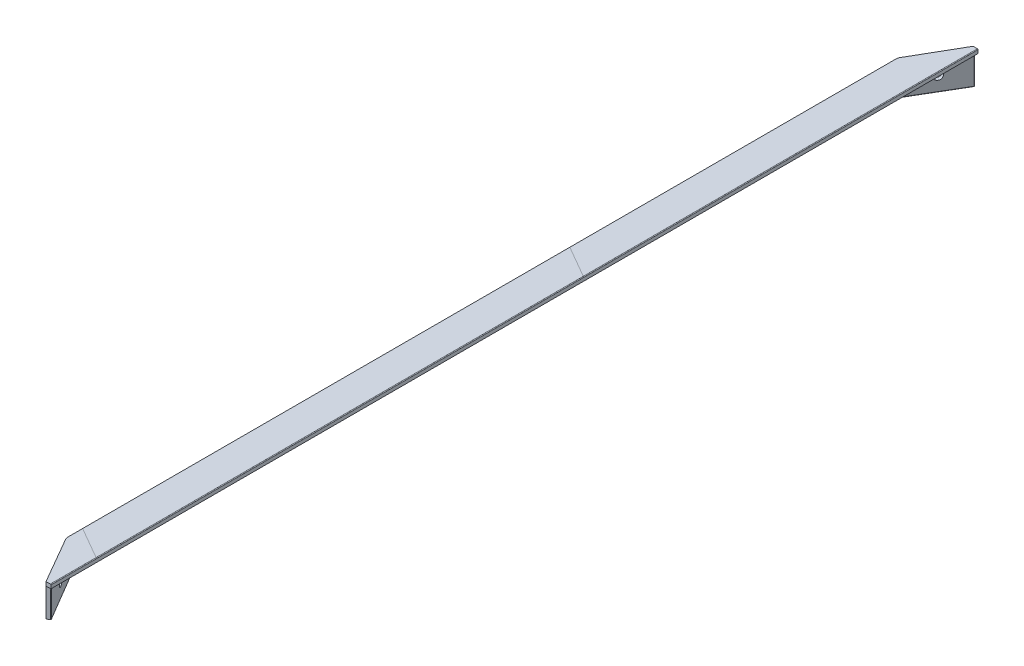
SolidWorks part; units mm, degrees
material "1.0116 (S235J2G3)"
ref_plane "Front Plane" through (0, 0, 0) normal (0, 0, 1) x (1, 0, 0)
ref_plane "Top Plane" through (0, 0, 0) normal (0, 1, 0) x (1, 0, 0)
ref_plane "Right Plane" through (0, 0, 0) normal (1, 0, 0) x (0, 0, -1)
sketch "Sketch1" plane through (0, 0, 0) normal (0, 0, 1) x (1, 0, 0)
  line L1 (44, 6) -> (44, 0)
  line L2 (44, 0) -> (0, 0)
  line L3 (0, 0) -> (0, -44)
  line L4 (0, -44) -> (-6, -44)
  line L6 (-6, -44) -> (-6, 6)
  line L7 (-6, 6) -> (44, 6)
  dimension "D1" = 0
  dimension "D2" = 6
  dimension "D3" = 6
  dimension "D4" = 6
  dimension "D5" = 50
  dimension "D6" = 50
  dimension "D7" = 0
extrude "Boss-Extrude1" add sketch "Sketch1" along normal blind 640
sketch "Sketch4" plane through (0, 0, 0) normal (0, 1, 0) x (1, 0, 0)
  line L0 (-6, -640) -> (36.5, -713.6122)
  line L1 (36.5, -713.6122) -> (44, -713.6122)
  line L2 (44, -713.6122) -> (44, -640)
  line L3 (44, -640) -> (-6, -640)
  line L4 (-6, -640) -> (-6, 0) construction
  dimension "D1" = 210
  dimension "D2" = 90
  dimension "D3" = 85
extrude "Boss-Extrude2" add sketch "Sketch4" along normal blind 6
sketch "Sketch5" plane through (0, 0, 0) normal (0, -1, 0) x (1, 0, 0)
  line L0 (-6, 640) -> (36.5, 713.6122)
  line L1 (36.5, 713.6122) -> (41.6962, 710.6122)
  line L3 (41.6962, 710.6122) -> (0, 640)
  line L4 (0, 640) -> (0, 0) construction
  line L5 (0, 640) -> (0, 0) construction
  line L6 (0, 640) -> (-6, 640)
  dimension "D1" = 6
extrude "Boss-Extrude3" add sketch "Sketch5" along normal blind 44
sketch "Sketch6" plane through (-280.2115, 0, 165.4636) normal (0.8611, 0, -0.5085) x (-0.5085, 0, -0.8611)
  line L0 (-551.0928, -44) -> (-633.0968, -44) construction
  line L1 (-633.0968, -44) -> (-633.0968, 0) construction
  circle A0 centre (-592.0968, -22) radius 6
  dimension "D1" = 12
  dimension "D2" = 22
  dimension "D3" = 41
extrude "Cut-Extrude1" cut sketch "Sketch6" against normal blind 6
mirror "Mirror4" about plane through (0, 0, 0) normal (0, 0, 1) of "Boss-Extrude2", "Cut-Extrude1", "Boss-Extrude3", "Boss-Extrude1"
fillet "Fillet1" radius 10 4 edges at (-6, -19, 640) (-6, -19, -640) (0, -22, -640) (0, -22, 640)
sketch "Sketch8" plane through (0, 6, 0) normal (0, 1, 0) x (1, 0, 0)
  line L0 (-6, -614.7446) -> (44, -643.6122)
  line L1 (-6, -637.3205) -> (-6, 637.3205) construction
  line L2 (44, -713.6122) -> (44, 713.6122) construction
  line L3 (44, -643.6122) -> (44, 106.3878)
  line L4 (44, 106.3878) -> (-6, 135.2554)
  line L5 (-6, 135.2554) -> (-6, -614.7446)
  line L6 (36.5, -713.6122) -> (44, -713.6122) construction
  dimension "D1" = 60
  dimension "D2" = 60
  dimension "D3" = 750
  dimension "D4" = 70
split line "Split Line1"
fillet "Fillet2" radius 4 5 edges at (21.5427, 0, 676.4824) (0.3535, 0, 639.9034) (21.5427, 0, -676.4824) (0.3535, 0, -639.9034) (0, 0, 0)
fillet "Fillet8" radius 1 17 edges at (44, 6, 678.6122) (44, 6, -410) (44, 6, 268.6122) (21.5427, -44, 676.4824) (0.3535, -44, 639.9034) (21.5427, -44, -676.4824) (0.3535, -44, -639.9034) (0, -44, 0) (15.9199, -44, 677.9663) (-5.6593, -44, 639.9087) (15.9199, -44, -677.9663) (-5.6593, -44, -639.9087) (-6, -44, 0) (42.4757, -1.2691, 710.1621) (41.6962, -23.917, 710.6122) (42.2178, -1.6937, -710.311) (41.6962, -23.917, -710.6122)
